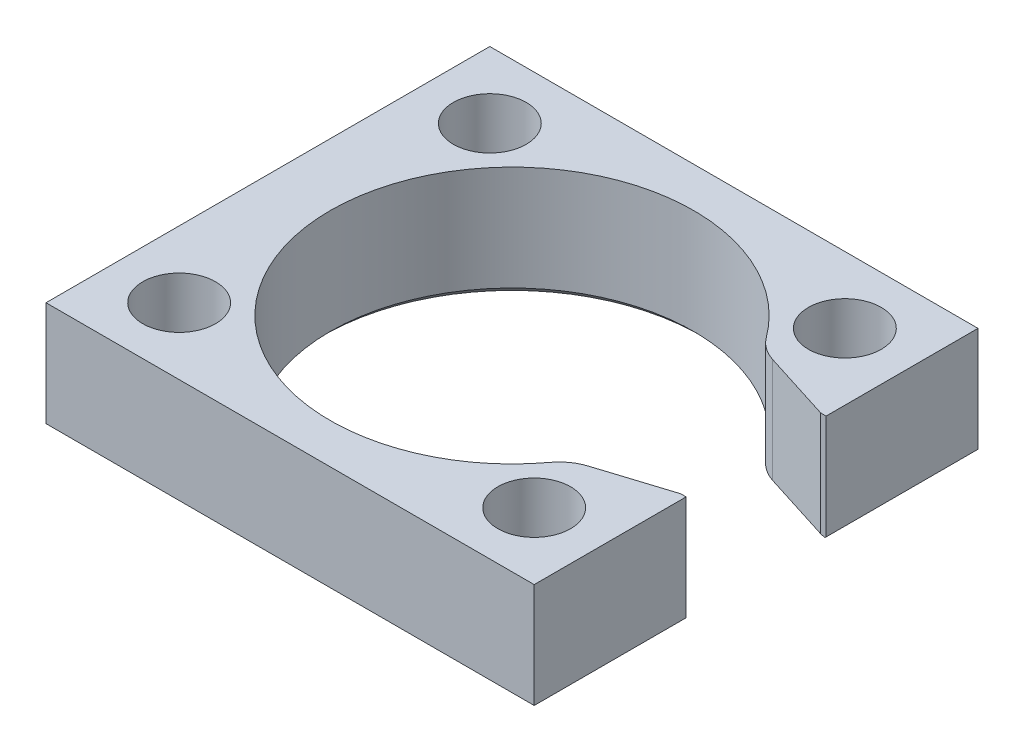
SolidWorks part; units mm, degrees
material "ABS"
ref_plane "Front Plane" through (0, 0, 0) normal (0, 0, 1) x (1, 0, 0)
ref_plane "Top Plane" through (0, 0, 0) normal (0, 1, 0) x (1, 0, 0)
ref_plane "Right Plane" through (0, 0, 0) normal (1, 0, 0) x (0, 0, -1)
sketch "Sketch1" plane through (0, 0, 0) normal (0, 1, 0) x (1, 0, 0)
  line L1 (-17.4625, -15.875) -> (17.4625, -15.875)
  line L2 (-17.4625, -15.875) -> (-17.4625, 15.875)
  line L3 (-17.4625, 15.875) -> (17.4625, 15.875)
  line L4 (17.4625, -15.875) -> (17.4625, 15.875)
  line L5 (-17.4625, -15.875) -> (17.4625, 15.875) construction
  line L6 (-17.4625, 15.875) -> (17.4625, -15.875) construction
  point P0 (0, 0)
  dimension "D1" = 34.925
  dimension "D2" = 31.75
extrude "Plate" add sketch "Sketch1" along normal mid plane 8
hole_wizard "#10 Clearance Hole1" positions "Sketch3" profile "Sketch2" hole size "#10" standard "ANSI Inch" end condition through all
sketch "Sketch3" plane through (0, 4, 0) normal (0, 1, 0) x (1, 0, 0)
  line L12 (12.7, -11.1125) -> (12.7, 11.1125)
  line L13 (12.7, 11.1125) -> (-12.7, 11.1125)
  line L14 (-12.7, 11.1125) -> (-12.7, -11.1125)
  line L15 (-12.7, -11.1125) -> (12.7, -11.1125)
  line L16 (12.7, -11.1125) -> (12.7, 11.1125)
  line L17 (12.7, 11.1125) -> (-12.7, 11.1125)
  line L18 (-12.7, 11.1125) -> (-12.7, -11.1125)
  line L19 (-12.7, -11.1125) -> (12.7, -11.1125)
  point P0 (-12.7, 11.1125)
  point P4 (12.7, 11.1125)
  point P6 (12.7, -11.1125)
  point P10 (-12.7, -11.1125)
  dimension "D1" = 4.7625
sketch "Sketch2" plane through (-12.7, 4, -11.1125) normal (1, 0, 0) x (0, 0, 1)
  line L0 (0, 0) -> (0, 8)
  line L1 (0, 8) -> (2.5527, 8)
  line L2 (2.5527, 8) -> (2.5527, 0)
  line L5 (2.5527, 0) -> (0, 0)
  line L11 (0, -6.35) -> (0, 107.95) construction
  dimension "Thru Hole Dia." = 5.1054
  dimension "Thru Hole Depth" = 8
sketch "Sketch4" plane through (0, 4, 0) normal (0, 1, 0) x (1, 0, 0)
  line L0 (10.6771, 6.5) -> (17, 4.5) construction
  line L1 (17, 4.5) -> (22.225, 4.5) construction
  line L2 (22.225, 4.5) -> (22.225, -4.5) construction
  line L3 (22.225, -4.5) -> (17, -4.5) construction
  line L4 (17, -4.5) -> (10.6771, -6.5) construction
  line L5 (-12.5, 0) -> (17, 0) construction
  line L6 (11.0099, 6.9275) -> (17.0784, 5.008)
  line L7 (17.0784, 5.008) -> (22.733, 5.008)
  line L8 (22.733, 5.008) -> (22.733, -5.008)
  line L9 (22.733, -5.008) -> (17.0784, -5.008)
  line L10 (17.0784, -5.008) -> (11.0099, -6.9275)
  arc A0 (10.6771, 6.5) -> (10.6771, -6.5) centre (0, 0) ccw construction
  arc A1 (11.0099, 6.9275) -> (11.0099, -6.9275) centre (0, 0) ccw
  arc A2 (10.6771, 6.5) -> (10.6771, -6.5) centre (0, 0) ccw construction
  dimension "D1" = 12.5
  dimension "D3" = 13
  dimension "D5" = 29.5
  dimension "D2" = 22.225
  dimension "D4" = 9
  dimension "D6" = 0.508
extrude "Load Cell Cutout" cut sketch "Sketch4" against normal up to next
fillet "Fillet1" radius 3.175 2 edges at (11.0099, 0, 6.9275) (11.0099, 0, -6.9275)
sketch "Sketch5" plane through (0, 4, 0) normal (0, 1, 0) x (1, 0, 0)
  circle A0 centre (-12.7, 11.1125) radius 2.6035
  circle A1 centre (12.7, 11.1125) radius 2.6035
  circle A2 centre (-12.7, -11.1125) radius 2.6035
  circle A3 centre (12.7, -11.1125) radius 2.6035
  dimension "D1" = 5.207
extrude "Cut-Extrude1" cut sketch "Sketch5" against normal up to next
chamfer "Chamfer1" distance 0.508 angle 45 14 edges at (11.1645, -4, -7.0412) (14.5652, -4, -5.803) (17.4625, -4, -10.4415) (0, -4, -15.875) (-17.4625, -4, 0) (0, -4, 15.875) (17.4625, -4, 10.4415) (14.5652, -4, 5.803) (11.1645, -4, 7.0412) (-13.008, -4, 0) (-12.7, -4, -13.716) (12.7, -4, -13.716) (-12.7, -4, 8.509) (12.7, -4, 8.509)
